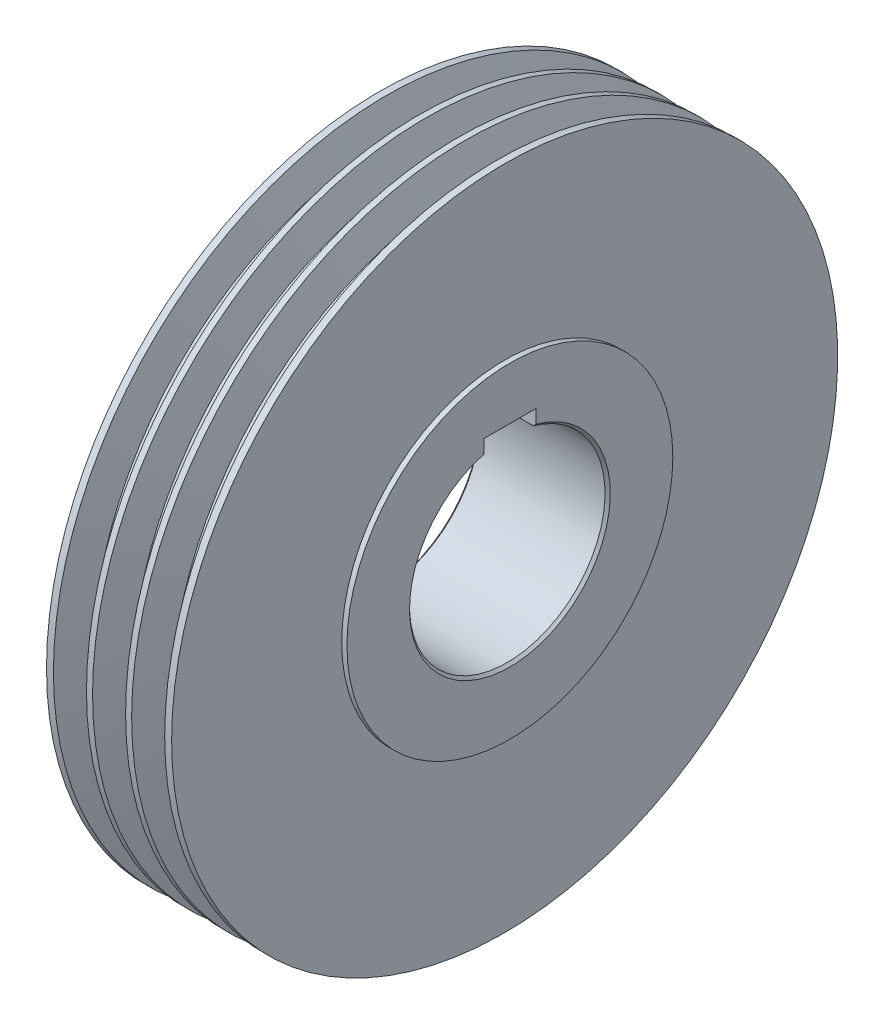
SolidWorks part; units mm, degrees
ref_plane "前视基准面" through (0, 0, 0) normal (0, 0, 1) x (1, 0, 0)
ref_plane "上视基准面" through (0, 0, 0) normal (0, 1, 0) x (1, 0, 0)
ref_plane "右视基准面" through (0, 0, 0) normal (1, 0, 0) x (0, 0, -1)
sketch "草图1" plane through (0, 0, 0) normal (0, 0, 1) x (1, 0, 0)
  line L0 (0, 0) -> (64.8368, 0) construction
  line L1 (0, 37.5) -> (0, 127.75)
  line L2 (0, 127.75) -> (48, 127.75)
  line L3 (48, 127.75) -> (48, 62.5)
  line L4 (48, 62.5) -> (50, 62.5)
  line L5 (50, 62.5) -> (50, 37.5)
  line L6 (50, 37.5) -> (0, 37.5)
  line L7 (2.6592, 127.75) -> (6.1599, 116.3) construction
  line L8 (6.1599, 116.3) -> (11.8401, 116.3) construction
  line L9 (11.8401, 116.3) -> (15.3408, 127.75) construction
  line L10 (0, 125) -> (48, 125) construction
  line L11 (9, 116.3) -> (9, 37.5) construction
  point P17 (3.5, 125)
  point P18 (14.5, 125)
  dimension "d2" = 255.5
  dimension "L" = 50
  dimension "B" = 48
  dimension "d" = 75
  dimension "d1" = 125
  dimension "dd" = 250
  dimension "f" = 9
  dimension "槽轮角" = 34
  dimension "bd" = 11
  dimension "hf" = 8.7
  dimension "ha" = 2.75
revolve "旋转1" add sketch "草图1" angle 360 about L0
sketch "草图2" plane through (0, 0, 0) normal (0, 0, 1) x (1, 0, 0)
  line L0 (11.8401, 116.3) -> (15.3408, 127.75) construction
  line L1 (6.1599, 116.3) -> (11.8401, 116.3) construction
  line L2 (2.6592, 127.75) -> (6.1599, 116.3) construction
  line L3 (11.8401, 116.3) -> (15.3408, 127.75)
  line L4 (6.1599, 116.3) -> (11.8401, 116.3)
  line L5 (2.6592, 127.75) -> (6.1599, 116.3)
  line L6 (2.6592, 127.75) -> (15.3408, 127.75)
  line L7 (0, 0) -> (48, 0) construction
  line L8 (48, -62.5) -> (48, 62.5) construction
revolve "切除-旋转1" cut sketch "草图2" angle 360 about L7
pattern_linear "阵列(线性)1" count 3 spacing 15 along (1, 0, 0) of "切除-旋转1"
chamfer "倒角1" distance 1 angle 45 2 edges at (50, 0, 37.5) (0, 0, 37.5)
sketch "草图4" plane through (0, 0, 0) normal (-1, 0, 0) x (0, 0, 1)
  line L1 (-10, 36.1421) -> (10, 36.1421)
  line L2 (-10, 36.1421) -> (-10, 42.4)
  line L3 (-10, 42.4) -> (10, 42.4)
  line L4 (10, 36.1421) -> (10, 42.4)
  circle A0 centre (0, 0) radius 37.5 construction
  point P6 (5.1, 42.4)
  dimension "键槽高度" = 42.4
  dimension "键槽宽度" = 20
  dimension "t1" = 4.9
extrude "切除-拉伸1" cut sketch "草图4" against normal through all
equation "\"B@草图1\" =  ( \"z@阵列(线性)1\" - 1 )  * \"e@阵列(线性)1\" +2 *  \"f@草图1\""
equation "\"键槽高度@草图4\" = \"d@草图1\" / 2  + \"t1@草图4\""
